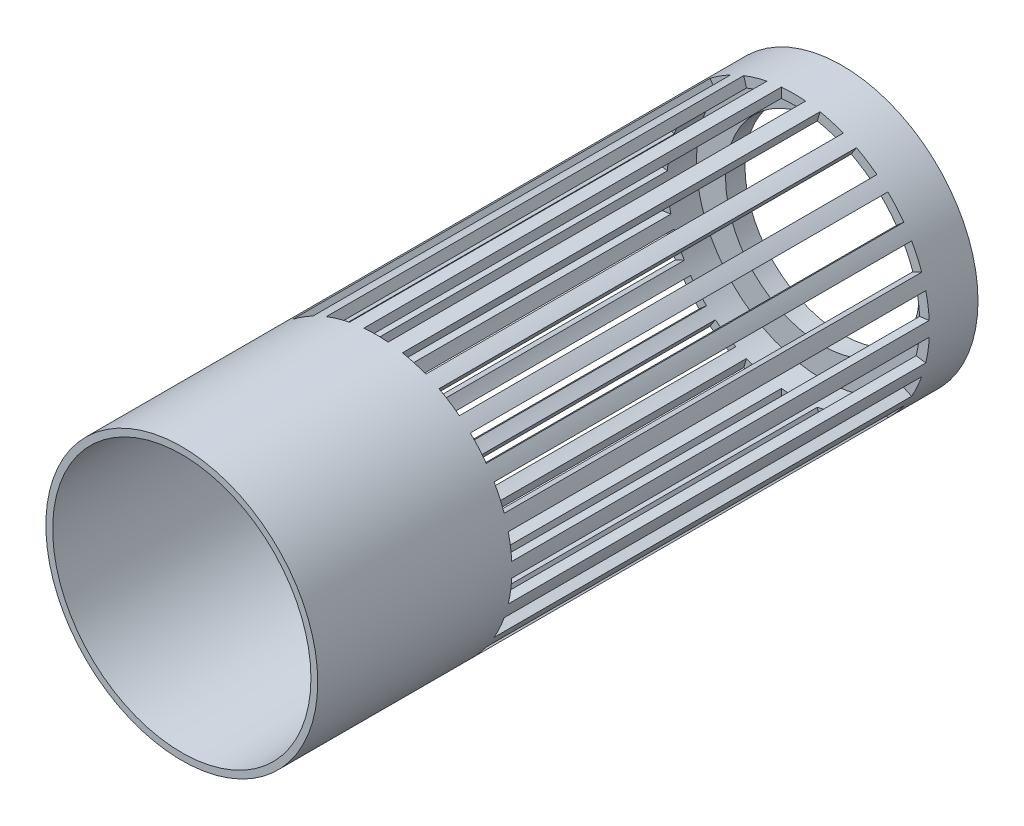
SolidWorks part; units mm, degrees
note: '?' marks a value the reader was unsure of. The reader was unsure of these and kept them because the rebuilt part matched: shared geometry of "스케치1<3>".
ref_plane "정면" through (0, 0, 0) normal (0, 0, 1) x (1, 0, 0)
ref_plane "윗면" through (0, 0, 0) normal (0, 1, 0) x (1, 0, 0)
ref_plane "우측면" through (0, 0, 0) normal (1, 0, 0) x (0, 0, -1)
sketch "스케치1" plane through (0, 0, 0) normal (0, 0, 1) x (1, 0, 0)
  circle A0 centre (0, 0) radius 6.5
  circle A1 centre (0, 0) radius 7
  dimension "D1" = 13
  dimension "D2" = 14
extrude "보스-돌출1" add sketch "스케치1" along normal blind 33
extrude "보스-돌출2" add sketch "스케치1<3>" against normal blind 1 contours A1
sketch "스케치1<3>" plane through (0, 0, 0) normal (0, 0, 1) x (1, 0, 0) same geometry as "스케치1"
sketch "스케치9" plane through (0, 0, 0) normal (0, 1, 0) x (1, 0, 0)
  line L0 (7, 1) -> (-7, 1) construction
  line L6 (0.625, 1) -> (0.625, -23)
  line L7 (0.625, -23) -> (-0.625, -23)
  line L8 (-0.625, 1) -> (-0.625, -23)
  line L9 (0, 0) -> (0, 6.1023) construction
  line L10 (-0.625, -1.5) -> (0.625, -1.5)
  point P14 (0, 0)
  point P15 (0, 0)
  dimension "D1" = 24
  dimension "D2" = 1.25
  dimension "D3" = 2.5
  dimension "D4" = 0.625
extrude "컷-돌출2" cut sketch "스케치9" against normal through all both and the other way through all contours L10 L8 L7 L6
pattern_circular "원형 패턴1" count 11 over 360 about axis through (0, 0, 0) along (0, 0, 1) of "컷-돌출2"
ref_axis "기준축1" through (0, 0, 33) along (0, 0, -1)?
sketch "스케치10" plane through (0, 0, 0) normal (0, 1, 0) x (1, 0, 0)
  line L0 (6.5, -33) -> (6.5, -23)
  line L1 (6.5, -33) -> (6.65, -33)
  line L2 (6.65, -33) -> (6.5, -23)
  dimension "D1" = 10
  dimension "D2" = 0.15
sweep "컷-스윕1" cut profiles "스케치10" path edge at (6.5, 0, 33)
sketch "스케치11" plane through (0, 0, -1) normal (0, 0, -1) x (-1, 0, 0)
  circle A0 centre (0, 0) radius 5
  dimension "D1" = 10
extrude "컷-돌출3" cut sketch "스케치11" against normal through all both and the other way through all
